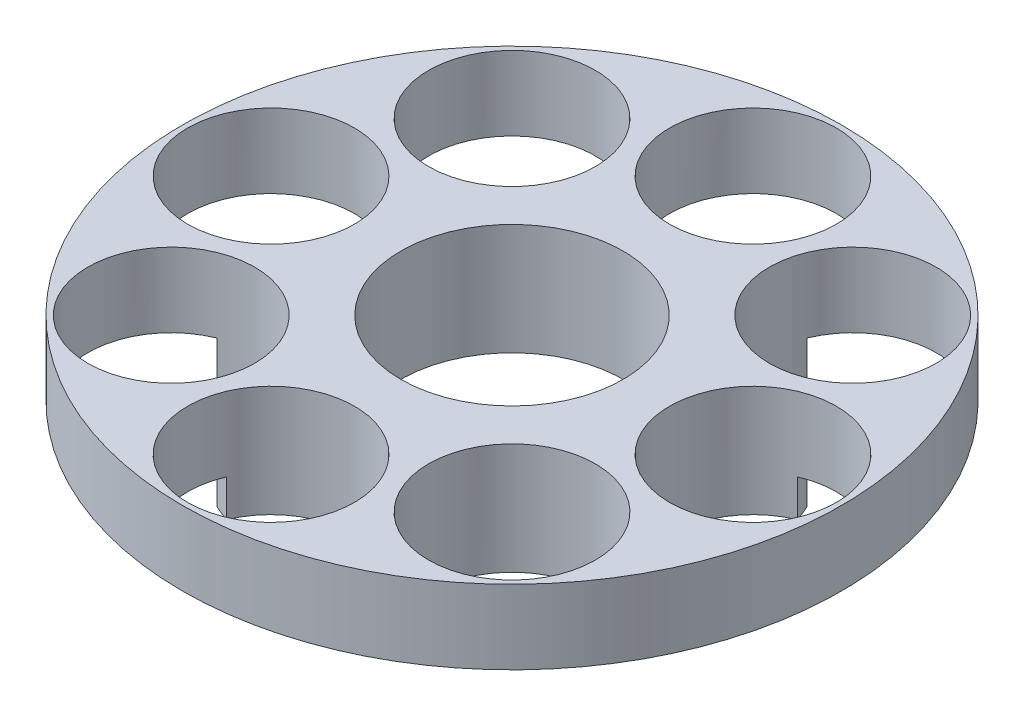
SolidWorks part; units mm, degrees
ref_plane "Front Plane" through (0, 0, 0) normal (0, 0, 1) x (1, 0, 0)
ref_plane "Top Plane" through (0, 0, 0) normal (0, 1, 0) x (1, 0, 0)
ref_plane "Right Plane" through (0, 0, 0) normal (1, 0, 0) x (0, 0, -1)
sketch "Sketch1" plane through (0, 0, 0) normal (0, 1, 0) x (1, 0, 0)
  line L0 (0, -164.5173) -> (0, 163.7587) construction
  line L1 (-88.9, 0) -> (190.5902, 0) construction
  line L2 (-148.2474, -148.2474) -> (81.4487, 81.4487) construction
  line L3 (101.0349, -101.0349) -> (-133.3884, 133.3884) construction
  circle A0 centre (0, 0) radius 88.9
  circle A1 centre (65, 0) radius 22.5
  circle A3 centre (45.9619, 45.9619) radius 22.5
  circle A4 centre (0, 65) radius 22.5
  circle A5 centre (-45.9619, 45.9619) radius 22.5
  circle A6 centre (-65, 0) radius 22.5
  circle A7 centre (-45.9619, -45.9619) radius 22.5
  circle A8 centre (0, -65) radius 22.5
  circle A10 centre (45.9619, -45.9619) radius 22.5
  circle A11 centre (0, 0) radius 30
  point P5 (0, 0)
  dimension "D1" = 177.8
  dimension "D4" = 45
  dimension "D5" = 65
  dimension "D7" = 65
  dimension "D8" = 65
  dimension "D9" = 65
  dimension "D10" = 65
  dimension "D11" = 65
  dimension "D12" = 65
  dimension "D14" = 60
  dimension "D2" = 45
  dimension "D3" = 45
  dimension "D6" = 65
  dimension "D13" = 65
extrude "Boss-Extrude1" add sketch "Sketch1" along normal blind 30
sketch "Sketch2" plane through (0, 30, 0) normal (0, 1, 0) x (1, 0, 0)
  circle A0 centre (0, 0) radius 60
  circle A1 centre (0, 0) radius 90
  dimension "D1" = 120
  dimension "D2" = 180
extrude "Cut-Extrude1" cut sketch "Sketch2" against normal blind 20 from offset 20 offset against normal yes
